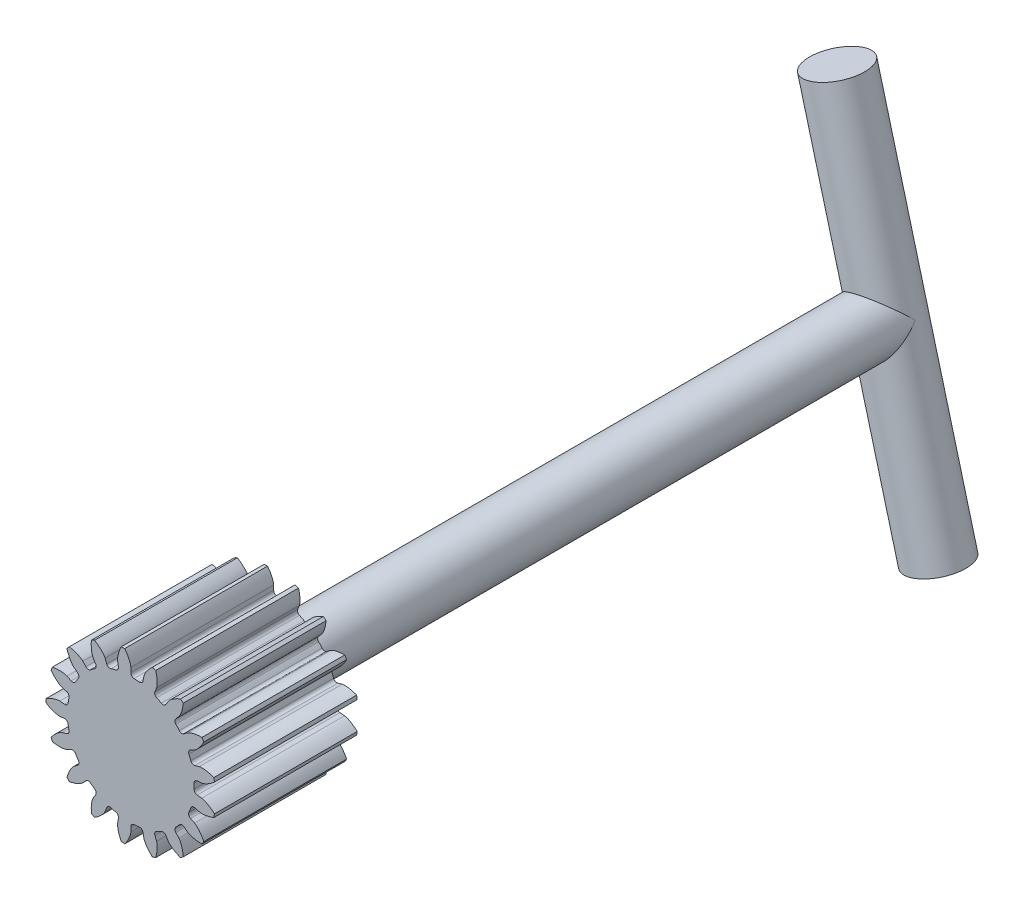
SolidWorks part; units mm, degrees
ref_plane "Front Plane" through (0, 0, 0) normal (0, 0, 1) x (1, 0, 0)
ref_plane "Top Plane" through (0, 0, 0) normal (0, 1, 0) x (1, 0, 0)
ref_plane "Right Plane" through (0, 0, 0) normal (1, 0, 0) x (0, 0, -1)
ref_axis "Gear Axis" through (0, 0, -95.5) along (0, 0, 1)
sketch "Blank Sketch" plane through (0, 0, 0) normal (0, 0, 1) x (1, 0, 0)
  circle A0 centre (0, 0) radius 11.875
  dimension "OD" = 23.75
extrude "Blank" add sketch "Blank Sketch" along normal blind 20
sketch "Tooth Space Sketch" plane through (0, 0, 0) normal (0, 0, 1) x (1, 0, 0)
  line L0 (9.9424, 0.9134) -> (9.2988, 0.8543)
  line L1 (9.9424, -0.9134) -> (9.2988, -0.8543)
  line L2 (12.7535, 3.1007) -> (12.7535, -3.1007)
  arc A0 (9.2988, 0.8543) -> (8.8676, 0.3619) centre (9.3422, 0.3813) ccw
  arc A1 (8.8676, -0.3619) -> (9.2988, -0.8543) centre (9.3422, -0.3813) ccw
  arc A2 (8.8676, -0.3619) -> (8.8676, 0.3619) centre (0, 0) ccw
  spline S0 degree 4 poles (9.9424, 0.9134) (9.9477, 0.914) (9.9627, 0.9159) (9.9908, 0.9208) (10.0364, 0.9304) (10.094, 0.9451) (10.1679, 0.9668) (10.254, 0.9959) (10.3477, 1.0316) (10.4483, 1.0743) (10.5475, 1.1204) (10.6453, 1.1696) (10.7417, 1.2214) (10.857, 1.2875) (10.9932, 1.3713) (11.1493, 1.4758) (11.3226, 1.602) (11.4947, 1.7386) (11.6604, 1.8795) (11.8233, 2.0291) (11.9776, 2.179) (12.1329, 2.3418) (12.2737, 2.4958) (12.4257, 2.676) (12.5467, 2.8236) (12.6999, 3.0262) (12.7884, 3.1482) (12.8897, 3.2936) (12.9335, 3.3596) (12.9605, 3.4002) knots 0 0 0 0 0 0.005377 0.015084 0.028532 0.04661 0.064855 0.092111 0.119476 0.146842 0.174209 0.201575 0.228941 0.256307 0.307035 0.361767 0.4165 0.471232 0.525964 0.580697 0.635429 0.690161 0.744894 0.799626 0.854358 0.909091 0.954545 1 1 1 1 1 construction
  spline S1 degree 4 poles (9.9424, 0.9134) (9.9477, 0.914) (9.9627, 0.9159) (9.9908, 0.9208) (10.0364, 0.9304) (10.094, 0.9451) (10.1679, 0.9668) (10.254, 0.9959) (10.3477, 1.0316) (10.4483, 1.0743) (10.5475, 1.1204) (10.6453, 1.1696) (10.7417, 1.2214) (10.857, 1.2875) (10.9932, 1.3713) (11.1493, 1.4758) (11.3226, 1.602) (11.4947, 1.7386) (11.6604, 1.8795) (11.8233, 2.0291) (11.9776, 2.179) (12.1329, 2.3418) (12.2737, 2.4958) (12.4257, 2.676) (12.5467, 2.8236) (12.6667, 2.9823) (12.7243, 3.0604) (12.7535, 3.1007) knots 0 0 0 0 0 0.005377 0.015084 0.028532 0.04661 0.064855 0.092111 0.119476 0.146842 0.174209 0.201575 0.228941 0.256307 0.307035 0.361767 0.4165 0.471232 0.525964 0.580697 0.635429 0.690161 0.744894 0.799626 0.854358 0.909091 0.909091 0.909091 0.909091 0.909091
  spline S2 degree 4 poles (9.9424, -0.9134) (9.9477, -0.914) (9.9627, -0.9159) (9.9908, -0.9208) (10.0364, -0.9304) (10.094, -0.9451) (10.1679, -0.9668) (10.254, -0.9959) (10.3477, -1.0316) (10.4483, -1.0743) (10.5475, -1.1204) (10.6453, -1.1696) (10.7417, -1.2214) (10.857, -1.2875) (10.9932, -1.3713) (11.1493, -1.4758) (11.3226, -1.602) (11.4947, -1.7386) (11.6604, -1.8795) (11.8233, -2.0291) (11.9776, -2.179) (12.1329, -2.3418) (12.2737, -2.4958) (12.4257, -2.676) (12.5467, -2.8236) (12.6999, -3.0262) (12.7884, -3.1482) (12.8897, -3.2936) (12.9335, -3.3596) (12.9605, -3.4002) knots 0 0 0 0 0 0.005377 0.015084 0.028532 0.04661 0.064855 0.092111 0.119476 0.146842 0.174209 0.201575 0.228941 0.256307 0.307035 0.361767 0.4165 0.471232 0.525964 0.580697 0.635429 0.690161 0.744894 0.799626 0.854358 0.909091 0.954545 1 1 1 1 1 construction
  spline S3 degree 4 poles (9.9424, -0.9134) (9.9477, -0.914) (9.9627, -0.9159) (9.9908, -0.9208) (10.0364, -0.9304) (10.094, -0.9451) (10.1679, -0.9668) (10.254, -0.9959) (10.3477, -1.0316) (10.4483, -1.0743) (10.5475, -1.1204) (10.6453, -1.1696) (10.7417, -1.2214) (10.857, -1.2875) (10.9932, -1.3713) (11.1493, -1.4758) (11.3226, -1.602) (11.4947, -1.7386) (11.6604, -1.8795) (11.8233, -2.0291) (11.9776, -2.179) (12.1329, -2.3418) (12.2737, -2.4958) (12.4257, -2.676) (12.5467, -2.8236) (12.6667, -2.9823) (12.7243, -3.0604) (12.7535, -3.1007) knots 0 0 0 0 0 0.005377 0.015084 0.028532 0.04661 0.064855 0.092111 0.119476 0.146842 0.174209 0.201575 0.228941 0.256307 0.307035 0.361767 0.4165 0.471232 0.525964 0.580697 0.635429 0.690161 0.744894 0.799626 0.854358 0.909091 0.909091 0.909091 0.909091 0.909091
  dimension "Root" = 8.875
  dimension "Fillet" = 0.475
extrude "Tooth Space" cut sketch "Tooth Space Sketch" against normal through all both and the other way through all both
pattern_circular "Teeth" count 17 over 360 about axis through (0, 0, -95.5) along (0, 0, 1) of "Tooth Space"
sketch "Bore Sketch" plane through (0, 0, 0) normal (0, 0, 1) x (1, 0, 0)
  circle A0 centre (0, 0) radius 4
  dimension "Bore" = 8
extrude "Bore" cut sketch "Bore Sketch" against normal through all both and the other way through all both
sketch "Sketch1" plane through (0, 0, 20) normal (0, 0, 1) x (1, 0, 0)
  circle A0 centre (0, 0) radius 4 construction
  circle A1 centre (0, 0) radius 4
extrude "Boss-Extrude1" add sketch "Sketch1" against normal blind 106
sketch "Sketch2" plane through (0, 0, 0) normal (-0.2576, 0.9662, 0) x (0, 0, -1)
  line L0 (86, -4) -> (86, 4) construction
  line L1 (86, -4) -> (86, 4) construction
  circle A0 centre (86, 0) radius 4
extrude "Boss-Extrude2" add sketch "Sketch2" along normal blind 27.5 and the other way blind 27.5
ref_plane "Cross Pin Plane" through (0, 0, 0) normal (-0.2576, 0.9662, 0) x (0, 0, 1)
equation "\"No. of Teeth\"= 17"
equation "\"Module\"= 1.25"
equation "\"Bore Diameter\"= 8"
equation "\"Pressure Angle\"= 20"
equation "\"Outer Diameter\"= ( \"No. of Teeth\" + 2 ) * \"Module\""
equation "\"Pitch Diameter\"= \"No. of Teeth\" * \"Module\""
equation "\"Backlash\"= IIF ( \"Module\" <= 1 , 0.3 * \"Module\" , 0.3 )"
equation "\"Arc Length\"= ( ( \"Module\" * pi ) / 2 + \"Backlash\" )"
equation "\"Fillet Radius\"= 0.38 * \"Module\""
equation "\"Tooth Depth\"= IIF ( \"Module\" <= 1.25 , \"Module\" * 2.4 , \"Module\" * 2.25 )"
equation "\"Face Width\"= 20"
equation "\"Root Diameter\"= \"Outer Diameter\" - 2 * \"Tooth Depth\""
equation "\"Base Diameter\"= \"Pitch Diameter\" * cos ( \"Pressure Angle\" )"
equation "\"Base Radius\"= \"Base Diameter\" / 2"
equation "\"Tooth Thickness\"= \"Module\" * pi - \"Arc Length\""
equation "\"Half Space Angle\"= ( \"Arc Length\" / \"Pitch Diameter\" ) * 180 / pi"
equation "\"Involute Fn\"= tan ( \"Pressure Angle\" ) - \"Pressure Angle\" * pi / 180"
equation "\"Flank Offset\"= \"Arc Length\" / \"Pitch Diameter\" - \"Involute Fn\""
equation "\"Tip Cap Diameter\"= \"Outer Diameter\" + 2 * \"Module\""
equation "\"Flank Start Diameter\"= IIF ( \"Base Diameter\" >= ( \"Root Diameter\" + 3 * \"Fillet Radius\" ) , \"Base Diameter\" , \"Root Diameter\" + 3 * \"Fillet Radius\" )"
equation "\"Involute t1\"= ( abs ( ( \"Flank Start Diameter\" / \"Base Diameter\" ) ^ 2 - 1 ) ) ^ 0.5"
equation "\"Involute t2\"= ( abs ( ( \"Tip Cap Diameter\" / \"Base Diameter\" ) ^ 2 - 1 ) ) ^ 0.5"
equation "\"Flank Arc Radius\"= ( \"Pitch Diameter\" / 2 ) * sin ( \"Pressure Angle\" )"
equation "\"Flank Centre Angle\"= \"Half Space Angle\" + \"Pressure Angle\""
equation "\"OD@Blank Sketch\"= \"Outer Diameter\""
equation "\"Width@Blank\"= \"Face Width\""
equation "\"Root@Tooth Space Sketch\"= \"Root Diameter\" / 2"
equation "\"Fillet@Tooth Space Sketch\"= \"Fillet Radius\""
equation "\"Count@Teeth\"= \"No. of Teeth\""
equation "\"Bore@Bore Sketch\"= \"Bore Diameter\""
